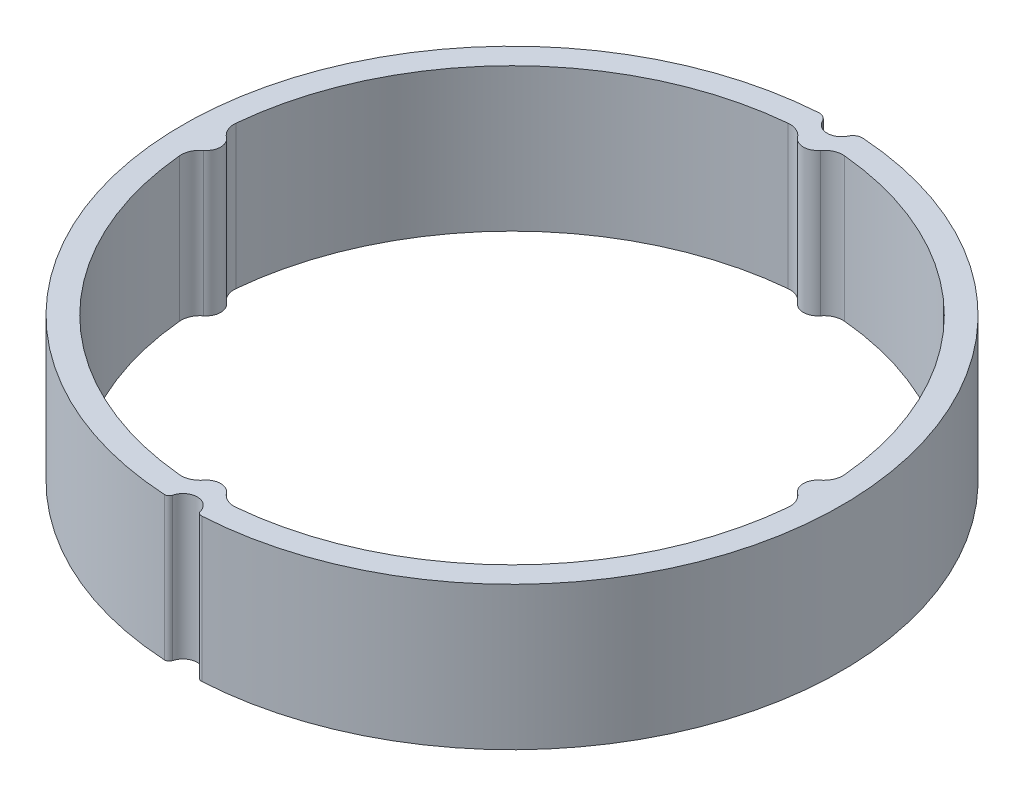
SolidWorks part; units mm, degrees
ref_plane "Front Plane" through (0, 0, 0) normal (0, 0, 1) x (1, 0, 0)
ref_plane "Top Plane" through (0, 0, 0) normal (0, 1, 0) x (1, 0, 0)
ref_plane "Right Plane" through (0, 0, 0) normal (1, 0, 0) x (0, 0, -1)
sketch "Sketch1" plane through (0, 0, 0) normal (0, 1, 0) x (1, 0, 0)
  line L3 (0, 0.002) -> (0, 3.7877) construction
  line L4 (0, 3.7877) -> (2.417, 3.7877)
  line L5 (0, 3.7877) -> (-2.417, 3.7877)
  arc A0 (1.9642, -34.442) -> (34.1982, 4.5552) centre (0, 0.002) ccw
  arc A2 (-2.417, 3.7877) -> (2.417, 3.7877) centre (0, 0.002) ccw
  circle A3 centre (0, 0.002) radius 34.5 construction
  arc A7 (-1.3541, 33.8562) -> (1.3541, 33.8562) centre (0, 34.5015) ccw
  arc A8 (34.1982, 4.5552) -> (2.3241, 34.4236) centre (0, 0.002) ccw
  arc A9 (-2.3241, 34.4236) -> (-34.1982, 4.5552) centre (0, 0.002) ccw
  arc A10 (-34.1982, 4.5552) -> (-1.9642, -34.442) centre (0, 0.002) ccw
  arc A11 (1.3541, 33.8562) -> (2.3241, 34.4236) centre (2.2568, 33.4259) cw
  arc A12 (-1.3541, 33.8562) -> (-2.3241, 34.4236) centre (-2.2568, 33.4259) ccw
  arc A13 (1.4518, -34.0686) -> (-1.4518, -34.0686) centre (0, -34.4457) ccw
  arc A14 (1.4518, -34.0686) -> (1.9642, -34.442) centre (1.9358, -33.9428) ccw
  arc A15 (-1.4518, -34.0686) -> (-1.9642, -34.442) centre (-1.9358, -33.9428) cw
  point P15 (1.4997, 34.4694)
  dimension "D2" = 4.834
  dimension "D3" = 4.4915
  dimension "D4" = 34.5
  dimension "D5" = 1
  dimension "D6" = 1.5
  dimension "D7" = 0.5
  dimension "D11" = 1.4997
sketch "Sketch2" plane through (0, 0, 0) normal (0, 1, 0) x (1, 0, 0)
  arc A0 (-31.8625, -2.9633) -> (-2.9633, -31.8625) centre (0, 0) ccw
  arc A1 (-1.1906, 31.0876) -> (1.1906, 31.0876) centre (0, 32) ccw
  arc A2 (31.0876, 1.1906) -> (31.0876, -1.1906) centre (32, 0) ccw
  arc A3 (1.1906, -31.0876) -> (-1.1906, -31.0876) centre (0, -32) ccw
  arc A4 (-31.0876, -1.1906) -> (-31.0876, 1.1906) centre (-32, 0) ccw
  arc A5 (-2.9633, 31.8625) -> (-31.8625, 2.9633) centre (0, 0) ccw
  arc A6 (31.8625, 2.9633) -> (2.9633, 31.8625) centre (0, 0) ccw
  arc A7 (2.9633, -31.8625) -> (31.8625, -2.9633) centre (0, 0) ccw
  arc A8 (-31.0876, -1.1906) -> (-31.8625, -2.9633) centre (-29.8711, -2.7781) ccw
  arc A9 (-31.0876, 1.1906) -> (-31.8625, 2.9633) centre (-29.8711, 2.7781) cw
  arc A10 (1.1906, -31.0876) -> (2.9633, -31.8625) centre (2.7781, -29.8711) ccw
  arc A11 (-1.1906, -31.0876) -> (-2.9633, -31.8625) centre (-2.7781, -29.8711) cw
  arc A12 (31.0876, 1.1906) -> (31.8625, 2.9633) centre (29.8711, 2.7781) ccw
  arc A13 (31.0876, -1.1906) -> (31.8625, -2.9633) centre (29.8711, -2.7781) cw
  arc A14 (1.1906, 31.0876) -> (2.9633, 31.8625) centre (2.7781, 29.8711) cw
  arc A15 (-1.1906, 31.0876) -> (-2.9633, 31.8625) centre (-2.7781, 29.8711) ccw
  point P21 (1.4996, -31.9648)
  point P26 (31.9648, 1.4996)
  point P33 (-1.4996, 31.9648)
  dimension "D1" = 32
  dimension "D2" = 1.5
  dimension "D3" = 1.5
  dimension "D4" = 1.5
  dimension "D5" = 1.5
  dimension "D6" = 2
extrude "Boss-Extrude1" add sketch "Sketch1" along normal blind 15 contours A10 A0 A8 A7 A9 A2 L5 L4 region at (2.2155, 0, 33.5591)
extrude "Cut-Extrude2" cut sketch "Sketch2" along normal through all
